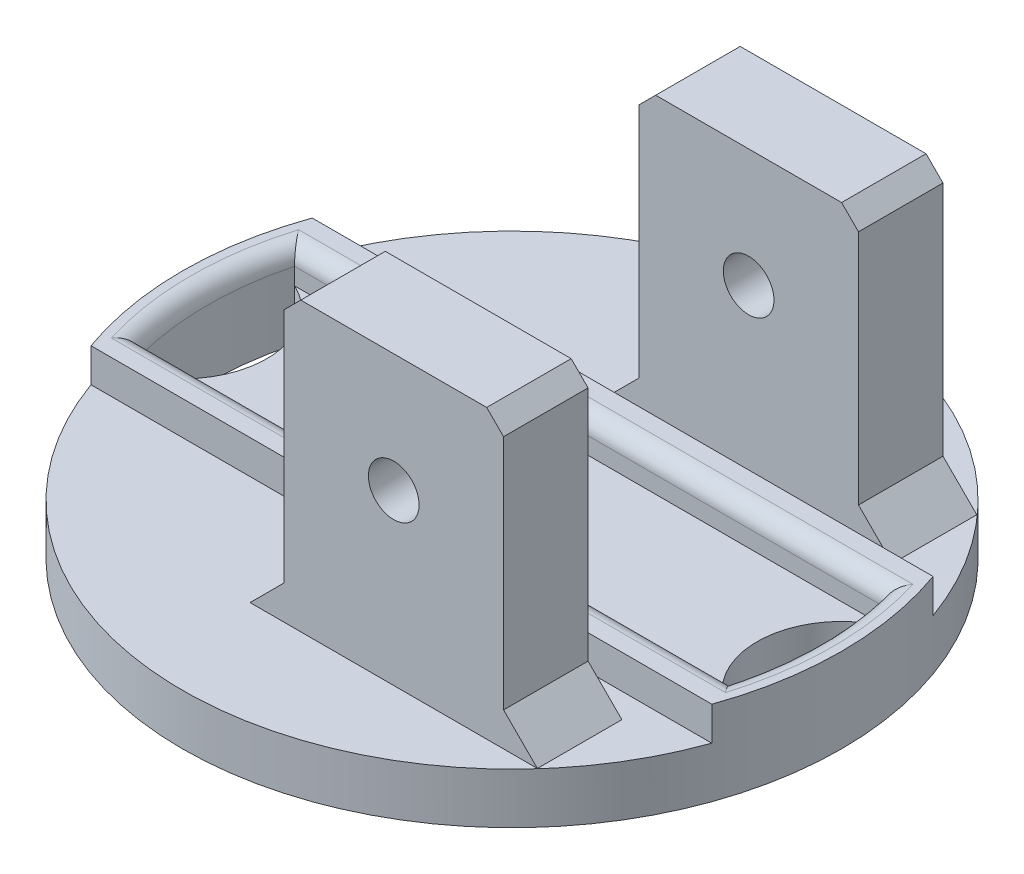
SolidWorks part; units mm, degrees
ref_plane "Front Plane" through (0, 0, 0) normal (0, 0, 1) x (1, 0, 0)
ref_plane "Top Plane" through (0, 0, 0) normal (0, 1, 0) x (1, 0, 0)
ref_plane "Right Plane" through (0, 0, 0) normal (1, 0, 0) x (0, 0, -1)
sketch "Sketch1" plane through (0, 0, 0) normal (0, 1, 0) x (1, 0, 0)
  line L0 (-24.765, 0) -> (24.765, 0) construction
  line L1 (0, 24.765) -> (0, -24.765) construction
  circle A0 centre (0, 0) radius 24.765
  arc A5 (-22.1192, 5.7725) -> (-22.1192, -5.7725) centre (0, 0) ccw
  arc A6 (-22.1192, 5.7725) -> (-22.1192, -5.7725) centre (-24.765, 0) cw
  arc A8 (22.1192, 5.7725) -> (22.1192, -5.7725) centre (24.765, 0) ccw
  arc A9 (22.1192, 5.7725) -> (22.1192, -5.7725) centre (0, 0) cw
  dimension "D1" = 49.53
  dimension "D2" = 6.35
  dimension "D3" = 1.905
extrude "plate" add sketch "Sketch1" along normal blind 3.81 contours A0 A5 A6 A8 A9 region at (0, 0, 0)
sketch "Sketch2" plane through (0, 3.81, 0) normal (0, 1, 0) x (1, 0, 0)
  line L0 (7.62, -10.16) -> (7.62, 10.16) construction
  line L1 (-0.635, 10.16) -> (15.875, 10.16)
  line L2 (-0.635, 10.16) -> (-0.635, 16.51)
  line L3 (-0.635, 16.51) -> (15.875, 16.51)
  line L4 (15.875, 16.51) -> (15.875, 10.16)
  line L5 (-18.415, 0) -> (18.415, 0) construction
  line L6 (-0.635, -16.51) -> (15.875, -16.51)
  line L7 (-0.635, -10.16) -> (-0.635, -16.51)
  line L8 (-0.635, -10.16) -> (15.875, -10.16)
  line L9 (15.875, -16.51) -> (15.875, -10.16)
  arc A2 (-22.1192, -5.7725) -> (-22.1192, 5.7725) centre (-24.765, 0) ccw construction
  arc A3 (22.1192, 5.7725) -> (22.1192, -5.7725) centre (24.765, 0) ccw construction
  point P6 (7.62, 10.16)
  point P17 (0, 0)
  dimension "D1" = 16.51
  dimension "D2" = 6.35
  dimension "D3" = 20.32
  dimension "D4" = 33.02
  dimension "D5" = 7.62
  dimension "D6" = 0.635
extrude "hook_uprights" add sketch "Sketch2" along normal blind 21.59
sketch "Sketch3" plane through (0, 0, -16.51) normal (0, 0, -1) x (-1, 0, 0)
  line L0 (-15.875, 16.51) -> (0.635, 16.51) construction
  line L1 (-15.875, 25.4) -> (-15.875, 3.81) construction
  line L2 (0.635, 25.4) -> (0.635, 3.81) construction
  line L3 (-15.875, 25.4) -> (0.635, 25.4) construction
  line L4 (23.9509, 6.35) -> (-23.9509, 6.35) construction
  circle A0 centre (-7.62, 16.51) radius 1.905
  point P13 (-7.62, 16.51)
  dimension "D2" = 3.81
  dimension "D1" = 8.89
  dimension "D3" = 10.16
extrude "hook_bolthole" cut sketch "Sketch3" against normal through all
sketch "Sketch4" plane through (0, 3.81, 0) normal (0, 1, 0) x (1, 0, 0)
  line L4 (-24.765, 0) -> (24.765, 0) construction
  line L9 (-22.1192, -5.7725) -> (22.1192, -5.7725)
  line L10 (-23.3282, -8.3125) -> (23.3282, -8.3125)
  line L12 (-22.1192, 5.7725) -> (22.1192, 5.7725)
  line L14 (-23.3282, 8.3125) -> (23.3282, 8.3125)
  arc A1 (-22.1192, -5.7725) -> (-22.1192, 5.7725) centre (0, 0) cw
  arc A5 (-22.1192, -5.7725) -> (-22.1192, 5.7725) centre (-24.765, 0) ccw construction
  circle A6 centre (0, 0) radius 24.765 construction
  arc A7 (-23.3282, -8.3125) -> (-23.3282, 8.3125) centre (0, 0) cw
  arc A8 (22.1192, 5.7725) -> (22.1192, -5.7725) centre (0, 0) cw
  arc A9 (23.3282, 8.3125) -> (23.3282, -8.3125) centre (0, 0) ccw
  point P15 (23.3282, -8.3125)
  point P17 (23.3282, -7.9067)
  circle M30 centre (0, 0) radius 24.765
  arc M31 (-22.1192, -5.7725) -> (-22.1192, 5.7725) centre (0, 0) cw
  arc M34 (22.1192, 5.7725) -> (22.1192, -5.7725) centre (0, 0) cw
  dimension "D1" = 2.54
  dimension "D2" = 2.54
extrude "Boss-Extrude1" add sketch "Sketch4" along normal blind 2.54 contours L4 A1 L12 L14 M30 M34 | L4 A9 L10 A8 L9 M30 M31 region at (0, 3.81, -6.3924) region at (0, 3.81, 6.3924)
fillet "Fillet1" radius 1.27 4 edges at (22.86, 6.35, 0) (0, 6.35, 5.7725) (-22.86, 6.35, 0) (0, 6.35, -5.7725)
chamfer "Chamfer1" distance 1.27 angle 45 4 edges at (15.875, 25.4, 13.335) (15.875, 25.4, -13.335) (-0.635, 25.4, 13.335) (-0.635, 25.4, -13.335)
chamfer "Chamfer2" distance 2.54 angle 45 4 edges at (-0.635, 3.81, -13.335) (15.875, 3.81, -13.335) (15.875, 3.81, 13.335) (-0.635, 3.81, 13.335)
